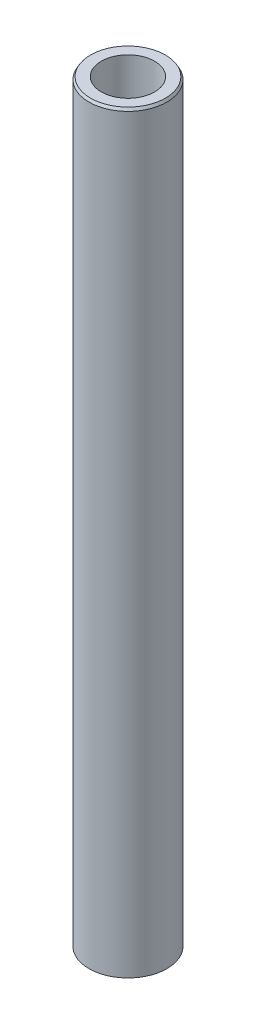
SolidWorks part; units mm, degrees
ref_plane "Front Plane" through (0, 0, 0) normal (0, 0, 1) x (1, 0, 0)
ref_plane "Top Plane" through (0, 0, 0) normal (0, 1, 0) x (1, 0, 0)
ref_plane "Right Plane" through (0, 0, 0) normal (1, 0, 0) x (0, 0, -1)
sketch "Sketch1" plane through (0, 0, 0) normal (0, 1, 0) x (1, 0, 0)
  circle A0 centre (0, 0) radius 27.5
  dimension "SHAFT_OD" = 55
extrude "Boss-Extrude1" add sketch "Sketch1" along normal blind 532.8251
sketch "Sketch2" plane through (0, 0, 0) normal (0, 1, 0) x (1, 0, 0)
  circle A0 centre (0, 0) radius 18.8215
  dimension "BORE_D" = 37.6429
extrude "Cut-Extrude1" cut sketch "Sketch2" along normal through all
chamfer "Chamfer1" distance 1.8749 angle 30 2 edges at (0, 532.8251, 27.5) (0, 0, 27.5) first distance on face at (0, 532.8251, 27.5) first distance on face at (0, 0, 18.8215)
